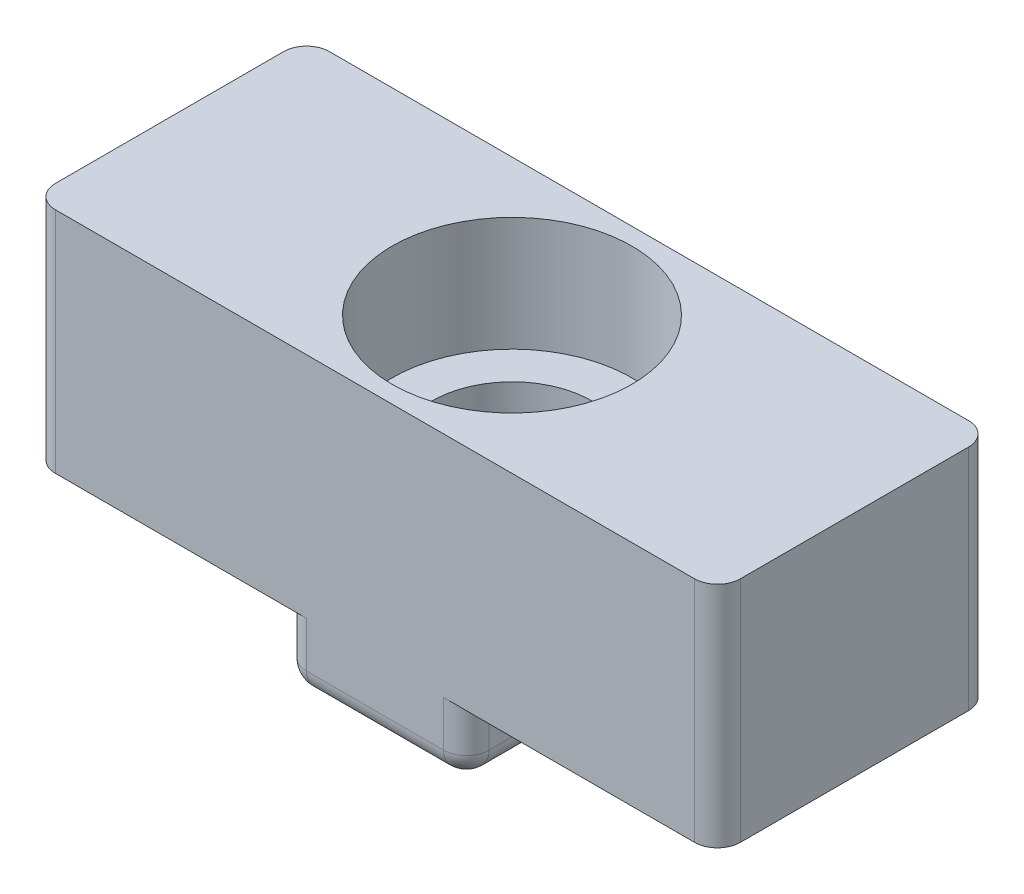
SolidWorks part; units mm, degrees
ref_plane "Front Plane" through (0, 0, 0) normal (0, 0, 1) x (1, 0, 0)
ref_plane "Top Plane" through (0, 0, 0) normal (0, 1, 0) x (1, 0, 0)
ref_plane "Right Plane" through (0, 0, 0) normal (1, 0, 0) x (0, 0, -1)
sketch "Sketch1" plane through (0, 0, 0) normal (0, 0, 1) x (1, 0, 0)
  line L0 (-15, 13) -> (-15, 3)
  line L1 (-15, 3) -> (-4, 3)
  line L2 (-4, 3) -> (-4, 0)
  line L3 (-4, 0) -> (4, 0)
  line L4 (4, 0) -> (4, 3)
  line L5 (4, 3) -> (15, 3)
  line L6 (15, 3) -> (15, 13)
  line L7 (15, 13) -> (-15, 13)
  line L8 (-19.5387, 0) -> (21.8549, 0) construction
  line L9 (0, -10.9725) -> (0, 12.8739) construction
  point P13 (0, 13)
  point P14 (0, 0)
  dimension "D1" = 8
  dimension "D2" = 3
  dimension "D3" = 30
  dimension "D4" = 10
extrude "Boss-Extrude1" add sketch "Sketch1" along normal mid plane 12
hole_wizard "CBORE for M6 SHCS1" positions "Sketch2" profile "Sketch3" counterbore size "M6" standard "ANSI Metric" end condition up to next
sketch "Sketch2" plane through (0, 13, 0) normal (0, 1, 0) x (1, 0, 0)
  point P0 (0, 0)
sketch "Sketch3" plane through (0, 13, 0) normal (1, 0, 0) x (0, 0, 1)
  line L0 (0, 0) -> (0, 13)
  line L1 (0, 13) -> (3.5, 13)
  line L3 (3.5, 13) -> (3.5, 5)
  line L4 (3.5, 5) -> (5.25, 5)
  line L5 (5.25, 5) -> (5.25, 0)
  line L7 (5.25, 0) -> (0, 0)
  line L11 (0, -6.35) -> (0, 107.95) construction
  dimension "Thru Hole Dia." = 7
  dimension "Thru Hole Depth" = 13
  dimension "C'Bore Dia." = 10.5
  dimension "C'Bore Depth" = 5
fillet "Fillet1" radius 1 12 edges at (4, 0, 0) (-4, 0, 0) (-4, 1.5, -6) (4, 1.5, 6) (4, 1.5, -6) (-4, 1.5, 6) (15, 8, -6) (15, 8, 6) (-15, 8, 6) (-15, 8, -6) (0, 0, -6) (0, 0, 6)
